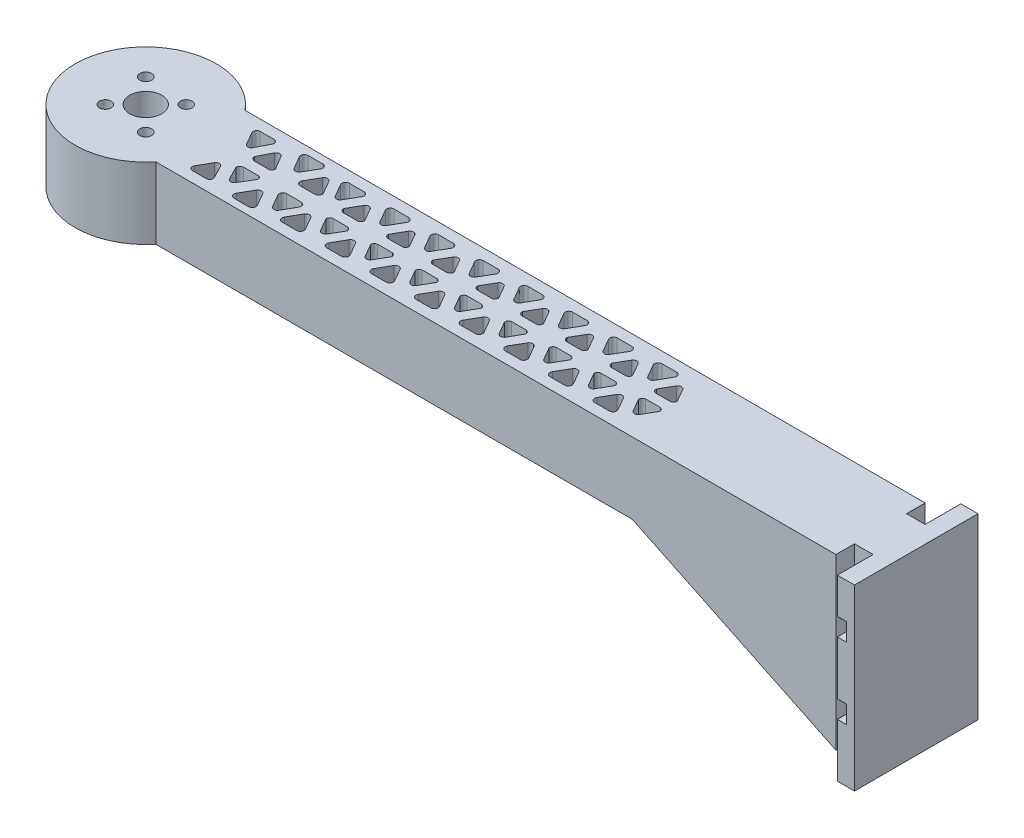
SolidWorks part; units mm, degrees
note: The reader was unsure of these and kept them because the rebuilt part matched: shared geometry of "Sketch2<4>".
ref_plane "Front Plane" through (0, 0, 0) normal (0, 0, 1) x (1, 0, 0)
ref_plane "Top Plane" through (0, 0, 0) normal (0, 1, 0) x (1, 0, 0)
ref_plane "Right Plane" through (0, 0, 0) normal (1, 0, 0) x (0, 0, -1)
sketch "Sketch1" plane through (0, 0, 0) normal (0, 1, 0) x (1, 0, 0)
  line L0 (19.7015, -0.0803) -> (215.7812, -0.0803) construction
  line L1 (15.2517, 12.4197) -> (215.7812, 12.4197)
  line L2 (15.2517, -12.5803) -> (215.7812, -12.5803)
  line L3 (215.7812, 12.4197) -> (215.7812, -12.5803)
  line L4 (22.4549, 9.4197) -> (26.384, 9.4197)
  line L5 (27.2449, 8.0014) -> (25.383, 4.4231)
  line L6 (23.682, 4.3855) -> (21.6147, 7.9638)
  line L7 (29.7182, 6.2554) -> (27.8031, 2.5747)
  line L8 (33.7755, 2.3958) -> (31.5736, 6.0947)
  line L9 (28.7602, 1.4197) -> (33.171, 1.4197)
  line L10 (37.9612, 5.1841) -> (40.0285, 8.7624)
  line L11 (34.1207, 8.7624) -> (36.188, 5.1841)
  line L12 (39.1419, 10.2986) -> (35.0073, 10.2986)
  line L13 (45.3949, 1.819) -> (41.2604, 1.819)
  line L14 (40.3733, 3.3543) -> (42.441, 6.9413)
  line L15 (44.2142, 6.9413) -> (46.2815, 3.363)
  line L16 (47.5213, 9.3393) -> (51.6558, 9.3393)
  line L17 (52.5425, 7.8032) -> (50.4752, 4.2249)
  line L18 (48.702, 4.2249) -> (46.6347, 7.8032)
  line L19 (54.955, 5.982) -> (52.8877, 2.4037)
  line L20 (58.7955, 2.3958) -> (56.7282, 5.982)
  line L21 (53.7743, 1.3393) -> (57.9089, 1.3393)
  line L22 (60.0313, 9.3393) -> (64.1658, 9.3393)
  line L23 (65.0525, 7.8032) -> (62.9852, 4.2249)
  line L24 (61.212, 4.2249) -> (59.1447, 7.8032)
  line L25 (67.465, 5.982) -> (65.3977, 2.4037)
  line L26 (71.3055, 2.3958) -> (69.2382, 5.982)
  line L27 (66.2843, 1.3393) -> (70.4189, 1.3393)
  line L28 (72.5413, 9.3393) -> (76.6758, 9.3393)
  line L29 (77.5625, 7.8032) -> (75.4952, 4.2249)
  line L30 (73.722, 4.2249) -> (71.6547, 7.8032)
  line L31 (79.975, 5.982) -> (77.9077, 2.4037)
  line L32 (83.8155, 2.3958) -> (81.7482, 5.982)
  line L33 (78.7943, 1.3393) -> (82.9289, 1.3393)
  line L34 (85.0513, 9.3393) -> (89.1858, 9.3393)
  line L35 (90.0725, 7.8032) -> (88.0052, 4.2249)
  line L36 (86.232, 4.2249) -> (84.1647, 7.8032)
  line L37 (92.485, 5.982) -> (90.4177, 2.4037)
  line L38 (96.3255, 2.3958) -> (94.2582, 5.982)
  line L39 (91.3043, 1.3393) -> (95.4389, 1.3393)
  line L40 (91.3043, -1.5) -> (95.4389, -1.5)
  line L41 (96.3255, -2.5565) -> (94.2582, -6.1427)
  line L42 (92.485, -6.1427) -> (90.4177, -2.5644)
  line L43 (86.232, -4.3855) -> (84.1647, -7.9638)
  line L44 (90.0725, -7.9638) -> (88.0052, -4.3855)
  line L45 (85.0513, -9.5) -> (89.1858, -9.5)
  line L46 (78.7943, -1.5) -> (82.9289, -1.5)
  line L47 (83.8155, -2.5565) -> (81.7482, -6.1427)
  line L48 (79.975, -6.1427) -> (77.9077, -2.5644)
  line L49 (73.722, -4.3855) -> (71.6547, -7.9638)
  line L50 (77.5625, -7.9638) -> (75.4952, -4.3855)
  line L51 (72.5413, -9.5) -> (76.6758, -9.5)
  line L52 (66.2843, -1.5) -> (70.4189, -1.5)
  line L53 (71.3055, -2.5565) -> (69.2382, -6.1427)
  line L54 (67.465, -6.1427) -> (65.3977, -2.5644)
  line L55 (61.212, -4.3855) -> (59.1447, -7.9638)
  line L56 (65.0525, -7.9638) -> (62.9852, -4.3855)
  line L57 (60.0313, -9.5) -> (64.1658, -9.5)
  line L58 (53.7743, -1.5) -> (57.9089, -1.5)
  line L59 (58.7955, -2.5565) -> (56.7282, -6.1427)
  line L60 (54.955, -6.1427) -> (52.8877, -2.5644)
  line L61 (48.702, -4.3855) -> (46.6347, -7.9638)
  line L62 (52.5425, -7.9638) -> (50.4752, -4.3855)
  line L63 (47.5213, -9.5) -> (51.6558, -9.5)
  line L64 (44.2142, -7.1019) -> (46.2815, -3.5236)
  line L65 (40.3733, -3.5149) -> (42.441, -7.1019)
  line L66 (45.3949, -1.9796) -> (41.2604, -1.9796)
  line L67 (39.1419, -10.4593) -> (35.0073, -10.4593)
  line L68 (34.1207, -8.9231) -> (36.188, -5.3448)
  line L69 (37.9612, -5.3448) -> (40.0285, -8.9231)
  line L70 (28.7602, -1.5803) -> (33.171, -1.5803)
  line L71 (33.7755, -2.5565) -> (31.5736, -6.2554)
  line L72 (29.7182, -6.4161) -> (27.8031, -2.7354)
  line L73 (23.682, -4.5462) -> (21.6147, -8.1245)
  line L74 (27.2449, -8.1621) -> (25.383, -4.5837)
  line L75 (22.4549, -9.5803) -> (26.384, -9.5803)
  line L76 (-0.0803, -16.7095) -> (-0.0803, 16.5488) construction
  line L77 (11.7312, -11.8919) -> (-11.8919, 11.7312) construction
  line L78 (-12.5321, -12.5321) -> (12.3715, 12.3715) construction
  line L79 (97.5613, 9.3393) -> (101.6958, 9.3393)
  line L80 (102.5825, 7.8032) -> (100.5152, 4.2249)
  line L81 (98.742, 4.2249) -> (96.6747, 7.8032)
  line L82 (104.995, 5.982) -> (102.9277, 2.4037)
  line L83 (108.8355, 2.3958) -> (106.7682, 5.982)
  line L84 (103.8143, 1.3393) -> (107.9489, 1.3393)
  line L85 (110.0713, 9.3393) -> (114.2058, 9.3393)
  line L86 (115.0925, 7.8032) -> (113.0252, 4.2249)
  line L87 (111.252, 4.2249) -> (109.1847, 7.8032)
  line L88 (117.505, 5.982) -> (115.4377, 2.4037)
  line L89 (121.3455, 2.3958) -> (119.2782, 5.982)
  line L90 (116.3243, 1.3393) -> (120.4589, 1.3393)
  line L91 (122.5813, 9.3393) -> (126.7158, 9.3393)
  line L92 (127.6025, 7.8032) -> (125.5352, 4.2249)
  line L93 (123.762, 4.2249) -> (121.6947, 7.8032)
  line L94 (130.015, 5.982) -> (127.9477, 2.4037)
  line L95 (133.8555, 2.3958) -> (131.7882, 5.982)
  line L96 (128.8343, 1.3393) -> (132.9689, 1.3393)
  line L97 (135.0913, 9.3393) -> (139.2258, 9.3393)
  line L98 (140.1125, 7.8032) -> (138.0452, 4.2249)
  line L99 (136.272, 4.2249) -> (134.2047, 7.8032)
  line L100 (142.525, 5.982) -> (140.4577, 2.4037)
  line L101 (146.3655, 2.3958) -> (144.2982, 5.982)
  line L102 (141.3443, 1.3393) -> (145.4789, 1.3393)
  line L139 (141.3443, -1.5) -> (145.4789, -1.5)
  line L140 (146.3655, -2.5565) -> (144.2982, -6.1427)
  line L141 (142.525, -6.1427) -> (140.4577, -2.5644)
  line L142 (136.272, -4.3855) -> (134.2047, -7.9638)
  line L143 (140.1125, -7.9638) -> (138.0452, -4.3855)
  line L144 (135.0913, -9.5) -> (139.2258, -9.5)
  line L145 (128.8343, -1.5) -> (132.9689, -1.5)
  line L146 (133.8555, -2.5565) -> (131.7882, -6.1427)
  line L147 (130.015, -6.1427) -> (127.9477, -2.5644)
  line L148 (123.762, -4.3855) -> (121.6947, -7.9638)
  line L149 (127.6025, -7.9638) -> (125.5352, -4.3855)
  line L150 (122.5813, -9.5) -> (126.7158, -9.5)
  line L151 (116.3243, -1.5) -> (120.4589, -1.5)
  line L152 (121.3455, -2.5565) -> (119.2782, -6.1427)
  line L153 (117.505, -6.1427) -> (115.4377, -2.5644)
  line L154 (111.252, -4.3855) -> (109.1847, -7.9638)
  line L155 (115.0925, -7.9638) -> (113.0252, -4.3855)
  line L156 (110.0713, -9.5) -> (114.2058, -9.5)
  line L157 (103.8143, -1.5) -> (107.9489, -1.5)
  line L158 (108.8355, -2.5565) -> (106.7682, -6.1427)
  line L159 (104.995, -6.1427) -> (102.9277, -2.5644)
  line L160 (98.742, -4.3855) -> (96.6747, -7.9638)
  line L161 (102.5825, -7.9638) -> (100.5152, -4.3855)
  line L162 (97.5613, -9.5) -> (101.6958, -9.5)
  line L163 (147.6013, 9.3393) -> (151.7358, 9.3393) [skipped]
  line L164 (152.6225, 7.8032) -> (150.5552, 4.2249) [skipped]
  line L165 (148.782, 4.2249) -> (146.7147, 7.8032) [skipped]
  line L166 (155.035, 5.982) -> (152.9677, 2.4037) [skipped]
  line L167 (158.8755, 2.3958) -> (156.8082, 5.982) [skipped]
  line L168 (153.8543, 1.3393) -> (157.9889, 1.3393) [skipped]
  line L169 (160.1113, 9.3393) -> (164.2458, 9.3393) [skipped]
  line L170 (165.1325, 7.8032) -> (163.0652, 4.2249) [skipped]
  line L171 (161.292, 4.2249) -> (159.2247, 7.8032) [skipped]
  line L172 (167.545, 5.982) -> (165.4777, 2.4037) [skipped]
  line L173 (171.3855, 2.3958) -> (169.3182, 5.982) [skipped]
  line L174 (166.3643, 1.3393) -> (170.4989, 1.3393) [skipped]
  line L175 (172.6213, 9.3393) -> (176.7558, 9.3393) [skipped]
  line L176 (177.6425, 7.8032) -> (175.5752, 4.2249) [skipped]
  line L177 (173.802, 4.2249) -> (171.7347, 7.8032) [skipped]
  line L178 (180.055, 5.982) -> (177.9877, 2.4037) [skipped]
  line L179 (183.8955, 2.3958) -> (181.8282, 5.982) [skipped]
  line L180 (178.8743, 1.3393) -> (183.0089, 1.3393) [skipped]
  circle A0 centre (-0.0803, -0.0803) radius 19.7818
  arc A1 (25.383, 4.4231) -> (23.682, 4.3855) centre (24.5222, 4.871) cw
  arc A2 (22.4549, 9.4197) -> (21.6147, 7.9638) centre (22.4549, 8.4493) ccw
  arc A3 (26.384, 9.4197) -> (27.2449, 8.0014) centre (26.384, 8.4493) cw
  arc A4 (33.171, 1.4197) -> (33.7755, 2.3958) centre (32.7524, 2.3541) ccw
  arc A5 (31.5736, 6.0947) -> (29.7182, 6.2554) centre (30.6092, 5.7508) ccw
  arc A6 (28.7602, 1.4197) -> (27.8031, 2.5747) centre (28.8569, 2.4738) cw
  arc A7 (35.0073, 10.2986) -> (34.1207, 8.7624) centre (35.0073, 9.2747) ccw
  arc A8 (39.1419, 10.2986) -> (40.0285, 8.7624) centre (39.1419, 9.2747) cw
  arc A9 (36.188, 5.1841) -> (37.9612, 5.1841) centre (37.0746, 5.6963) ccw
  arc A10 (45.3949, 1.819) -> (46.2815, 3.363) centre (45.3995, 2.8429) ccw
  arc A11 (42.441, 6.9413) -> (44.2142, 6.9413) centre (43.3276, 6.4291) cw
  arc A12 (41.2604, 1.819) -> (40.3733, 3.3543) centre (41.2604, 2.8429) cw
  arc A13 (50.4752, 4.2249) -> (48.702, 4.2249) centre (49.5886, 4.7371) cw
  arc A14 (47.5213, 9.3393) -> (46.6347, 7.8032) centre (47.5213, 8.3154) ccw
  arc A15 (51.6558, 9.3393) -> (52.5425, 7.8032) centre (51.6558, 8.3154) cw
  arc A16 (57.9089, 1.3393) -> (58.7955, 2.3958) centre (57.7724, 2.3541) ccw
  arc A17 (56.7282, 5.982) -> (54.955, 5.982) centre (55.8416, 5.4698) ccw
  arc A18 (53.7743, 1.3393) -> (52.8877, 2.4037) centre (53.9105, 2.3542) cw
  arc A19 (62.9852, 4.2249) -> (61.212, 4.2249) centre (62.0986, 4.7371) cw
  arc A20 (60.0313, 9.3393) -> (59.1447, 7.8032) centre (60.0313, 8.3154) ccw
  arc A21 (64.1658, 9.3393) -> (65.0525, 7.8032) centre (64.1658, 8.3154) cw
  arc A22 (70.4189, 1.3393) -> (71.3055, 2.3958) centre (70.2824, 2.3541) ccw
  arc A23 (69.2382, 5.982) -> (67.465, 5.982) centre (68.3516, 5.4698) ccw
  arc A24 (66.2843, 1.3393) -> (65.3977, 2.4037) centre (66.4205, 2.3542) cw
  arc A25 (75.4952, 4.2249) -> (73.722, 4.2249) centre (74.6086, 4.7371) cw
  arc A26 (72.5413, 9.3393) -> (71.6547, 7.8032) centre (72.5413, 8.3154) ccw
  arc A27 (76.6758, 9.3393) -> (77.5625, 7.8032) centre (76.6758, 8.3154) cw
  arc A28 (82.9289, 1.3393) -> (83.8155, 2.3958) centre (82.7924, 2.3541) ccw
  arc A29 (81.7482, 5.982) -> (79.975, 5.982) centre (80.8616, 5.4698) ccw
  arc A30 (78.7943, 1.3393) -> (77.9077, 2.4037) centre (78.9305, 2.3542) cw
  arc A31 (88.0052, 4.2249) -> (86.232, 4.2249) centre (87.1186, 4.7371) cw
  arc A32 (85.0513, 9.3393) -> (84.1647, 7.8032) centre (85.0513, 8.3154) ccw
  arc A33 (89.1858, 9.3393) -> (90.0725, 7.8032) centre (89.1858, 8.3154) cw
  arc A34 (95.4389, 1.3393) -> (96.3255, 2.3958) centre (95.3024, 2.3541) ccw
  arc A35 (94.2582, 5.982) -> (92.485, 5.982) centre (93.3716, 5.4698) ccw
  arc A36 (91.3043, 1.3393) -> (90.4177, 2.4037) centre (91.4405, 2.3542) cw
  arc A37 (91.3043, -1.5) -> (90.4177, -2.5644) centre (91.4405, -2.5148) ccw
  arc A38 (94.2582, -6.1427) -> (92.485, -6.1427) centre (93.3716, -5.6305) cw
  arc A39 (95.4389, -1.5) -> (96.3255, -2.5565) centre (95.3024, -2.5148) cw
  arc A40 (89.1858, -9.5) -> (90.0725, -7.9638) centre (89.1858, -8.4761) ccw
  arc A41 (85.0513, -9.5) -> (84.1647, -7.9638) centre (85.0513, -8.4761) cw
  arc A42 (88.0052, -4.3855) -> (86.232, -4.3855) centre (87.1186, -4.8978) ccw
  arc A43 (78.7943, -1.5) -> (77.9077, -2.5644) centre (78.9305, -2.5148) ccw
  arc A44 (81.7482, -6.1427) -> (79.975, -6.1427) centre (80.8616, -5.6305) cw
  arc A45 (82.9289, -1.5) -> (83.8155, -2.5565) centre (82.7924, -2.5148) cw
  arc A46 (76.6758, -9.5) -> (77.5625, -7.9638) centre (76.6758, -8.4761) ccw
  arc A47 (72.5413, -9.5) -> (71.6547, -7.9638) centre (72.5413, -8.4761) cw
  arc A48 (75.4952, -4.3855) -> (73.722, -4.3855) centre (74.6086, -4.8978) ccw
  arc A49 (66.2843, -1.5) -> (65.3977, -2.5644) centre (66.4205, -2.5148) ccw
  arc A50 (69.2382, -6.1427) -> (67.465, -6.1427) centre (68.3516, -5.6305) cw
  arc A51 (70.4189, -1.5) -> (71.3055, -2.5565) centre (70.2824, -2.5148) cw
  arc A52 (64.1658, -9.5) -> (65.0525, -7.9638) centre (64.1658, -8.4761) ccw
  arc A53 (60.0313, -9.5) -> (59.1447, -7.9638) centre (60.0313, -8.4761) cw
  arc A54 (62.9852, -4.3855) -> (61.212, -4.3855) centre (62.0986, -4.8978) ccw
  arc A55 (53.7743, -1.5) -> (52.8877, -2.5644) centre (53.9105, -2.5148) ccw
  arc A56 (56.7282, -6.1427) -> (54.955, -6.1427) centre (55.8416, -5.6305) cw
  arc A57 (57.9089, -1.5) -> (58.7955, -2.5565) centre (57.7724, -2.5148) cw
  arc A58 (51.6558, -9.5) -> (52.5425, -7.9638) centre (51.6558, -8.4761) ccw
  arc A59 (47.5213, -9.5) -> (46.6347, -7.9638) centre (47.5213, -8.4761) cw
  arc A60 (50.4752, -4.3855) -> (48.702, -4.3855) centre (49.5886, -4.8978) ccw
  arc A61 (41.2604, -1.9796) -> (40.3733, -3.5149) centre (41.2604, -3.0036) ccw
  arc A62 (42.441, -7.1019) -> (44.2142, -7.1019) centre (43.3276, -6.5897) ccw
  arc A63 (45.3949, -1.9796) -> (46.2815, -3.5236) centre (45.3995, -3.0036) cw
  arc A64 (36.188, -5.3448) -> (37.9612, -5.3448) centre (37.0746, -5.857) cw
  arc A65 (39.1419, -10.4593) -> (40.0285, -8.9231) centre (39.1419, -9.4353) ccw
  arc A66 (35.0073, -10.4593) -> (34.1207, -8.9231) centre (35.0073, -9.4353) cw
  arc A67 (28.7602, -1.5803) -> (27.8031, -2.7354) centre (28.8569, -2.6345) ccw
  arc A68 (31.5736, -6.2554) -> (29.7182, -6.4161) centre (30.6092, -5.9115) cw
  arc A69 (33.171, -1.5803) -> (33.7755, -2.5565) centre (32.7524, -2.5148) cw
  arc A70 (26.384, -9.5803) -> (27.2449, -8.1621) centre (26.384, -8.61) ccw
  arc A71 (22.4549, -9.5803) -> (21.6147, -8.1245) centre (22.4549, -8.61) cw
  arc A72 (25.383, -4.5837) -> (23.682, -4.5462) centre (24.5222, -5.0316) ccw
  circle A73 centre (-6.7979, 6.6372) radius 1.65
  circle A74 centre (5.5765, 5.5765) radius 1.65
  circle A75 centre (6.6372, -6.7979) radius 1.65
  circle A76 centre (-5.7372, -5.7372) radius 1.65
  circle A77 centre (-0.0803, -0.0803) radius 4.5
  arc A78 (100.5152, 4.2249) -> (98.742, 4.2249) centre (99.6286, 4.7371) cw
  arc A79 (97.5613, 9.3393) -> (96.6747, 7.8032) centre (97.5613, 8.3154) ccw
  arc A80 (101.6958, 9.3393) -> (102.5825, 7.8032) centre (101.6958, 8.3154) cw
  arc A81 (107.9489, 1.3393) -> (108.8355, 2.3958) centre (107.8124, 2.3541) ccw
  arc A82 (106.7682, 5.982) -> (104.995, 5.982) centre (105.8816, 5.4698) ccw
  arc A83 (103.8143, 1.3393) -> (102.9277, 2.4037) centre (103.9505, 2.3542) cw
  arc A84 (113.0252, 4.2249) -> (111.252, 4.2249) centre (112.1386, 4.7371) cw
  arc A85 (110.0713, 9.3393) -> (109.1847, 7.8032) centre (110.0713, 8.3154) ccw
  arc A86 (114.2058, 9.3393) -> (115.0925, 7.8032) centre (114.2058, 8.3154) cw
  arc A87 (120.4589, 1.3393) -> (121.3455, 2.3958) centre (120.3224, 2.3541) ccw
  arc A88 (119.2782, 5.982) -> (117.505, 5.982) centre (118.3916, 5.4698) ccw
  arc A89 (116.3243, 1.3393) -> (115.4377, 2.4037) centre (116.4605, 2.3542) cw
  arc A90 (125.5352, 4.2249) -> (123.762, 4.2249) centre (124.6486, 4.7371) cw
  arc A91 (122.5813, 9.3393) -> (121.6947, 7.8032) centre (122.5813, 8.3154) ccw
  arc A92 (126.7158, 9.3393) -> (127.6025, 7.8032) centre (126.7158, 8.3154) cw
  arc A93 (132.9689, 1.3393) -> (133.8555, 2.3958) centre (132.8324, 2.3541) ccw
  arc A94 (131.7882, 5.982) -> (130.015, 5.982) centre (130.9016, 5.4698) ccw
  arc A95 (128.8343, 1.3393) -> (127.9477, 2.4037) centre (128.9705, 2.3542) cw
  arc A96 (138.0452, 4.2249) -> (136.272, 4.2249) centre (137.1586, 4.7371) cw
  arc A97 (135.0913, 9.3393) -> (134.2047, 7.8032) centre (135.0913, 8.3154) ccw
  arc A98 (139.2258, 9.3393) -> (140.1125, 7.8032) centre (139.2258, 8.3154) cw
  arc A99 (145.4789, 1.3393) -> (146.3655, 2.3958) centre (145.3424, 2.3541) ccw
  arc A100 (144.2982, 5.982) -> (142.525, 5.982) centre (143.4116, 5.4698) ccw
  arc A101 (141.3443, 1.3393) -> (140.4577, 2.4037) centre (141.4805, 2.3542) cw
  arc A138 (141.3443, -1.5) -> (140.4577, -2.5644) centre (141.4805, -2.5148) ccw
  arc A139 (144.2982, -6.1427) -> (142.525, -6.1427) centre (143.4116, -5.6305) cw
  arc A140 (145.4789, -1.5) -> (146.3655, -2.5565) centre (145.3424, -2.5148) cw
  arc A141 (139.2258, -9.5) -> (140.1125, -7.9638) centre (139.2258, -8.4761) ccw
  arc A142 (135.0913, -9.5) -> (134.2047, -7.9638) centre (135.0913, -8.4761) cw
  arc A143 (138.0452, -4.3855) -> (136.272, -4.3855) centre (137.1586, -4.8978) ccw
  arc A144 (128.8343, -1.5) -> (127.9477, -2.5644) centre (128.9705, -2.5148) ccw
  arc A145 (131.7882, -6.1427) -> (130.015, -6.1427) centre (130.9016, -5.6305) cw
  arc A146 (132.9689, -1.5) -> (133.8555, -2.5565) centre (132.8324, -2.5148) cw
  arc A147 (126.7158, -9.5) -> (127.6025, -7.9638) centre (126.7158, -8.4761) ccw
  arc A148 (122.5813, -9.5) -> (121.6947, -7.9638) centre (122.5813, -8.4761) cw
  arc A149 (125.5352, -4.3855) -> (123.762, -4.3855) centre (124.6486, -4.8978) ccw
  arc A150 (116.3243, -1.5) -> (115.4377, -2.5644) centre (116.4605, -2.5148) ccw
  arc A151 (119.2782, -6.1427) -> (117.505, -6.1427) centre (118.3916, -5.6305) cw
  arc A152 (120.4589, -1.5) -> (121.3455, -2.5565) centre (120.3224, -2.5148) cw
  arc A153 (114.2058, -9.5) -> (115.0925, -7.9638) centre (114.2058, -8.4761) ccw
  arc A154 (110.0713, -9.5) -> (109.1847, -7.9638) centre (110.0713, -8.4761) cw
  arc A155 (113.0252, -4.3855) -> (111.252, -4.3855) centre (112.1386, -4.8978) ccw
  arc A156 (103.8143, -1.5) -> (102.9277, -2.5644) centre (103.9505, -2.5148) ccw
  arc A157 (106.7682, -6.1427) -> (104.995, -6.1427) centre (105.8816, -5.6305) cw
  arc A158 (107.9489, -1.5) -> (108.8355, -2.5565) centre (107.8124, -2.5148) cw
  arc A159 (101.6958, -9.5) -> (102.5825, -7.9638) centre (101.6958, -8.4761) ccw
  arc A160 (97.5613, -9.5) -> (96.6747, -7.9638) centre (97.5613, -8.4761) cw
  arc A161 (100.5152, -4.3855) -> (98.742, -4.3855) centre (99.6286, -4.8978) ccw
  arc A162 (150.5552, 4.2249) -> (148.782, 4.2249) centre (149.6686, 4.7371) cw [skipped]
  arc A163 (147.6013, 9.3393) -> (146.7147, 7.8032) centre (147.6013, 8.3154) ccw [skipped]
  arc A164 (151.7358, 9.3393) -> (152.6225, 7.8032) centre (151.7358, 8.3154) cw [skipped]
  arc A165 (157.9889, 1.3393) -> (158.8755, 2.3958) centre (157.8524, 2.3541) ccw [skipped]
  arc A166 (156.8082, 5.982) -> (155.035, 5.982) centre (155.9216, 5.4698) ccw [skipped]
  arc A167 (153.8543, 1.3393) -> (152.9677, 2.4037) centre (153.9905, 2.3542) cw [skipped]
  arc A168 (163.0652, 4.2249) -> (161.292, 4.2249) centre (162.1786, 4.7371) cw [skipped]
  arc A169 (160.1113, 9.3393) -> (159.2247, 7.8032) centre (160.1113, 8.3154) ccw [skipped]
  arc A170 (164.2458, 9.3393) -> (165.1325, 7.8032) centre (164.2458, 8.3154) cw [skipped]
  arc A171 (170.4989, 1.3393) -> (171.3855, 2.3958) centre (170.3624, 2.3541) ccw [skipped]
  arc A172 (169.3182, 5.982) -> (167.545, 5.982) centre (168.4316, 5.4698) ccw [skipped]
  arc A173 (166.3643, 1.3393) -> (165.4777, 2.4037) centre (166.5005, 2.3542) cw [skipped]
  arc A174 (175.5752, 4.2249) -> (173.802, 4.2249) centre (174.6886, 4.7371) cw [skipped]
  arc A175 (172.6213, 9.3393) -> (171.7347, 7.8032) centre (172.6213, 8.3154) ccw [skipped]
  arc A176 (176.7558, 9.3393) -> (177.6425, 7.8032) centre (176.7558, 8.3154) cw [skipped]
  arc A177 (183.0089, 1.3393) -> (183.8955, 2.3958) centre (182.8724, 2.3541) ccw [skipped]
  arc A178 (181.8282, 5.982) -> (180.055, 5.982) centre (180.9416, 5.4698) ccw [skipped]
  arc A179 (178.8743, 1.3393) -> (177.9877, 2.4037) centre (179.0105, 2.3542) cw [skipped]
  point P5 (-0.0803, -0.0803)
  point P8 (-0.0803, -0.0803)
  point P55 (30.6092, 5.7508)
  point P66 (37.0746, 5.6963)
  point P74 (43.3276, 6.4291)
  point P93 (55.8416, 5.4698)
  point P112 (68.3516, 5.4698)
  point P131 (80.8616, 5.4698)
  point P150 (93.3716, 5.4698)
  point P239 (93.3716, -5.6305)
  point P240 (80.8616, -5.6305)
  point P241 (68.3516, -5.6305)
  point P242 (55.8416, -5.6305)
  point P243 (43.3276, -6.5897)
  point P244 (37.0746, -5.857)
  point P245 (30.6092, -5.9115)
  point P247 (-0.0803, -0.0803)
  point P256 (180.9416, 5.4698)
  point P257 (168.4316, 5.4698)
  point P276 (105.8816, 5.4698)
  point P295 (118.3916, 5.4698)
  point P314 (130.9016, 5.4698)
  point P333 (143.4116, 5.4698)
  point P334 (155.9216, 5.4698)
  point P518 (143.4116, -5.6305)
  point P519 (130.9016, -5.6305)
  point P520 (118.3916, -5.6305)
  point P521 (105.8816, -5.6305)
  dimension "D7" = 3.3
  dimension "D8" = 3.3
  dimension "D9" = 3.3
  dimension "D10" = 3.3
  dimension "D15" = 9
  dimension "D1" = 3
  dimension "D2" = 3
  dimension "D3" = 25
  dimension "D4" = 3
  dimension "D5" = 45
  dimension "D6" = 90
  dimension "D11" = 9.5
  dimension "D12" = 9.5
  dimension "D13" = 8
  dimension "D14" = 8
  dimension "D16" = 8
extrude "Boss-Extrude1" add sketch "Sketch1" along normal blind 20
sketch "Sketch2" plane through (0, 20, 0) normal (0, 1, 0) x (1, 0, 0)
  line L0 (215.7812, 12.4197) -> (215.7812, 17.2197)
  line L1 (215.7812, 17.2197) -> (210.9812, 17.2197)
  line L2 (210.9812, 17.2197) -> (210.9812, -12.5803)
  line L3 (15.2517, -12.5803) -> (215.7812, -12.5803) construction
  line L4 (210.9812, -12.5803) -> (210.9812, -17.3803)
  line L5 (210.9812, -17.3803) -> (215.7812, -17.3803)
  line L6 (215.7812, -17.3803) -> (215.7812, -12.5803)
  line L7 (215.7812, -12.5803) -> (215.7812, 12.4197)
  line L8 (210.9812, -12.5803) -> (205.7812, -12.5803)
  line L17 (205.7812, -12.5803) -> (205.7812, -7.3803)
  line L18 (205.7812, -7.3803) -> (210.9812, -7.3803)
  line L19 (205.7812, 12.4197) -> (205.7812, 7.2197)
  line L20 (15.2517, 12.4197) -> (215.7812, 12.4197) construction
  line L21 (205.7812, 7.2197) -> (210.9812, 7.2197)
  line L22 (205.7812, 12.4197) -> (210.9812, 12.4197)
  line L23 (210.9812, 12.4197) -> (210.9812, 7.2197)
  line L24 (210.9812, -7.3803) -> (210.9812, -12.5803)
  dimension "D1" = 4.8
  dimension "D2" = 4.8
  dimension "D3" = 5.2
  dimension "D4" = 5.2
  dimension "D5" = 5.2
  dimension "D6" = 4.8
extrude "Boss-Extrude2" add sketch "Sketch2" against normal blind 50 contours L6 L7 L0 L1 L2 L4 L5
sketch "Sketch3" plane through (0, 0, 12.5803) normal (0, 0, 1) x (1, 0, 0)
  line L8 (210.9812, 0) -> (148.7812, 0)
  line L9 (15.2517, 0) -> (210.9812, 0) construction
  line L10 (210.9812, 0) -> (210.9812, -30)
  line L11 (210.9812, -30) -> (210.9812, 20) construction
  line L12 (210.9812, -30) -> (148.7812, 0)
extrude "Boss-Extrude3" add sketch "Sketch3" against normal up to surface (25 mm away) up to face at (113.1165, 10, -12.4197)
extrude "Cut-Extrude1" cut sketch "Sketch2<4>" against normal up to surface (50 mm away) contours L22 L19 L21 L2 | L18 L17 L8 L2
sketch "Sketch2<4>" plane through (0, 20, 0) normal (0, 1, 0) x (1, 0, 0) same geometry as "Sketch2"
sketch "Sketch4" plane through (0, 0, 17.3803) normal (0, 0, 1) x (1, 0, 0)
  line L0 (210.9812, -30) -> (210.9812, 20) construction
  line L1 (208.4812, 5) -> (213.4812, 5)
  line L2 (208.4812, 5) -> (208.4812, 10)
  line L3 (208.4812, 10) -> (213.4812, 10)
  line L4 (213.4812, 5) -> (213.4812, 10)
  line L5 (208.4812, 5) -> (213.4812, 10) construction
  line L6 (208.4812, 10) -> (213.4812, 5) construction
  line L7 (208.4812, 10) -> (208.4812, 5)
  line L8 (208.4812, -15) -> (213.4812, -15)
  line L9 (208.4812, -15) -> (208.4812, -10)
  line L10 (208.4812, -10) -> (213.4812, -10)
  line L11 (213.4812, -15) -> (213.4812, -10)
  line L12 (208.4812, -15) -> (213.4812, -10) construction
  line L13 (208.4812, -10) -> (213.4812, -15) construction
  line L14 (208.4812, 10) -> (208.3812, 10)
  line L15 (208.4812, 5) -> (208.3812, 5)
  line L16 (208.3812, 10) -> (208.3812, 5)
  line L17 (208.3812, -10) -> (208.3812, -15)
  line L18 (208.4812, -15) -> (208.3812, -15)
  line L19 (208.4812, -10) -> (208.3812, -10)
  line L20 (208.4812, -15) -> (208.4812, -10)
  line L21 (208.4812, -10) -> (208.4812, -15)
  point P0 (210.9812, 7.5)
  point P7 (210.9812, -12.5)
  line M7 (210.9812, 20) -> (210.9812, -30)
  dimension "D1" = 5
  dimension "D2" = 5
  dimension "D3" = 5
  dimension "D4" = 5
  dimension "D5" = 10
  dimension "D6" = 15
  dimension "D7" = 0.1
extrude "Cut-Extrude2" cut sketch "Sketch4" against normal up to surface (34.6 mm away) contours L10 L9 L8 M7 | L8 L11 L10 M7 | L3 L2 L1 M7 | L1 L4 L3 M7 | L9 L19 L17 L18 | L14 L16 L15 L2
